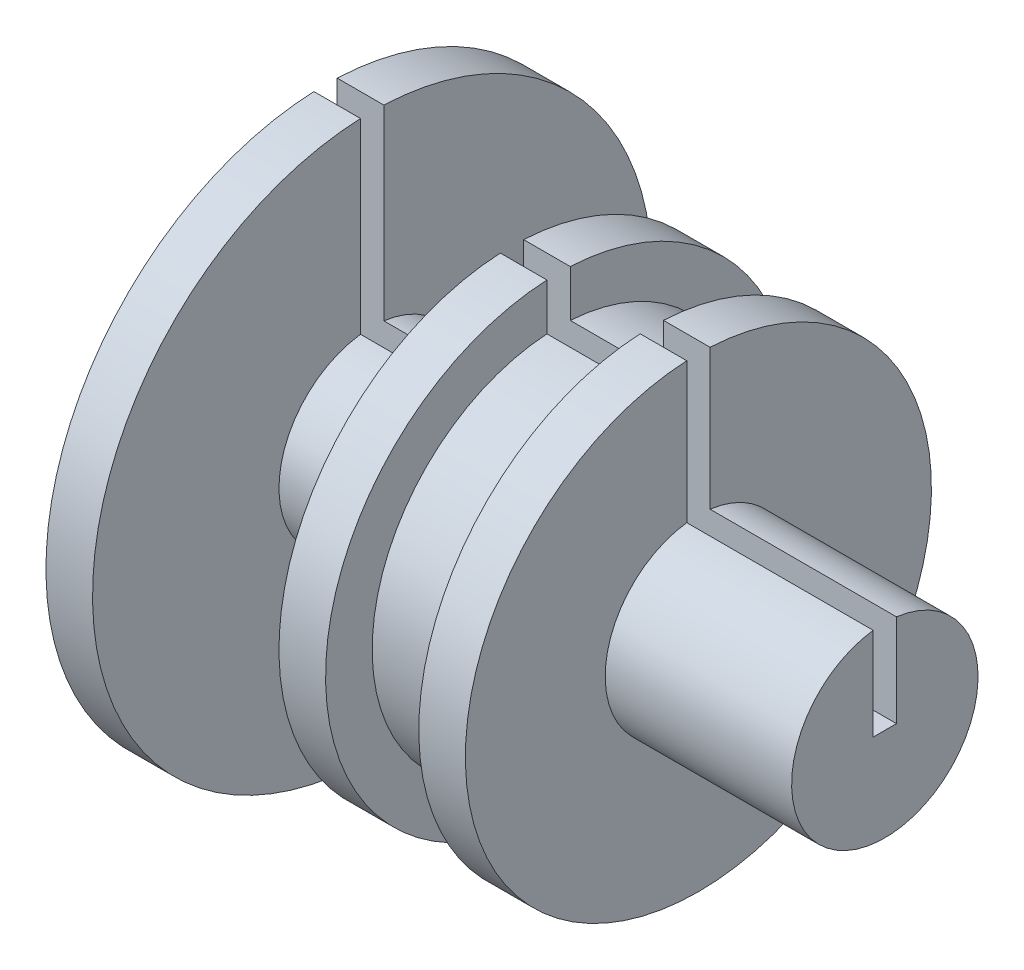
SolidWorks part; units mm, degrees
ref_plane "Front Plane" through (0, 0, 0) normal (0, 0, 1) x (1, 0, 0)
ref_plane "Top Plane" through (0, 0, 0) normal (0, 1, 0) x (1, 0, 0)
ref_plane "Right Plane" through (0, 0, 0) normal (1, 0, 0) x (0, 0, -1)
sketch "Sketch1" plane through (0, 0, 0) normal (0, 0, 1) x (1, 0, 0)
  line L0 (0, 0) -> (60, 0) construction
  line L2 (20, 10) -> (5, 10)
  line L3 (20, 10) -> (20, 25)
  line L4 (20, 25) -> (25, 25)
  line L5 (25, 25) -> (25, 20)
  line L6 (25, 20) -> (35, 20)
  line L7 (35, 25) -> (35, 20)
  line L8 (40, 25) -> (35, 25)
  line L9 (40, 10) -> (40, 25)
  line L10 (60, 10) -> (40, 10)
  line L11 (60, 0) -> (60, 10)
  line L12 (30, 0) -> (30, 40) construction
  line L13 (0, 0) -> (60, 0)
  line L14 (5, 10) -> (5, 30)
  line L15 (5, 30) -> (0, 30)
  line L16 (0, 30) -> (0, 0)
  point P3 (5.1249, 8.8895)
  point P4 (6.641, 5.8542)
  point P13 (30, 20)
  dimension "D1" = 5
  dimension "D2" = 10
  dimension "D3" = 50
  dimension "D4" = 5
  dimension "D5" = 30
  dimension "D6" = 20
  dimension "D7" = 5
revolve "Revolve1" add sketch "Sketch1" angle 360 about L13
sketch "Sketch2" plane through (60, 0, 0) normal (1, 0, 0) x (0, 0, -1)
  line L1 (-1.25, 34.957) -> (1.25, 34.957)
  line L2 (-1.25, 34.957) -> (-1.25, 0)
  line L3 (-1.25, 0) -> (1.25, 0)
  line L4 (1.25, 34.957) -> (1.25, 0)
  point P4 (0, 0)
  dimension "D1" = 34.957
  dimension "D2" = 2.5
extrude "Cut-Extrude1" cut sketch "Sketch2" against normal through all
